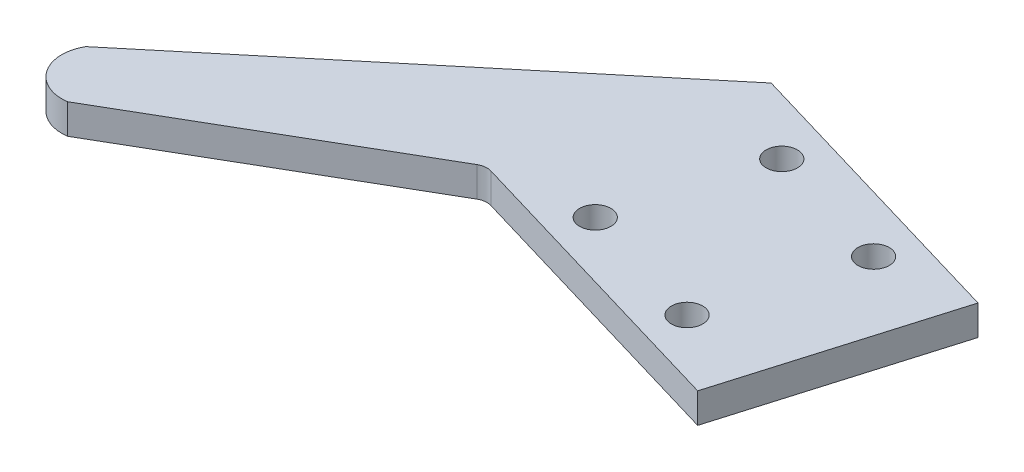
SolidWorks part; units mm, degrees
material "6061 Alloy"
ref_plane "Front Plane" through (0, 0, 0) normal (0, 0, 1) x (1, 0, 0)
ref_plane "Top Plane" through (0, 0, 0) normal (0, 1, 0) x (1, 0, 0)
ref_plane "Right Plane" through (0, 0, 0) normal (1, 0, 0) x (0, 0, -1)
sketch "Sketch1" plane through (0, 0, 0) normal (0, 1, 0) x (1, 0, 0)
  line L1 (22.9946, -31.525) -> (-18.2047, -55.4154)
  line L4 (81.9229, -10.7327) -> (71.7331, -45.1328)
  line L5 (71.7331, -45.1328) -> (24.9902, -31.2869)
  line L6 (81.9229, -10.7327) -> (35.1799, 3.1132)
  line L7 (35.1799, 3.1132) -> (-24.3516, -46.3783)
  arc A0 (-18.2047, -55.4154) -> (-24.3516, -46.3783) centre (-19.075, -49.3983) cw
  arc A2 (22.9946, -31.525) -> (24.9902, -31.2869) centre (24.2688, -33.7223) cw
  dimension "D1" = 2.54
  dimension "D2" = 35.8775
  dimension "D3" = 47.625
extrude "Boss-Extrude1" add sketch "Sketch1" along normal blind 4.7625
sketch "Sketch2" plane through (0, 4.7625, 0) normal (0, 1, 0) x (1, 0, 0)
  line L0 (35.1799, 3.1132) -> (71.7331, -45.1328) construction
  line L1 (53.4565, -21.0098) -> (63.8314, -24.083) construction
  line L3 (63.8314, -24.083) -> (67.2219, -12.6366) construction
  line L6 (63.8314, -24.083) -> (60.4408, -35.5294) construction
  line L7 (53.4565, -21.0098) -> (43.0817, -17.9366) construction
  line L8 (43.0817, -17.9366) -> (46.4723, -6.4903) construction
  line L9 (43.0817, -17.9366) -> (39.6911, -29.383) construction
  line L10 (53.4565, -21.0098) -> (58.5514, -3.8098) construction
  line L11 (81.9229, -10.7327) -> (35.1799, 3.1132) construction
  dimension "D1" = 21.6408
hole_wizard "#10 Clearance Hole1" positions "Sketch3" profile "Sketch4" hole size "#10" standard "ANSI Inch" end condition through all
sketch "Sketch3" plane through (0, 4.7625, 0) normal (0, 1, 0) x (1, 0, 0)
  point P0 (39.6911, -29.383)
  point P3 (46.4723, -6.4903)
  point P6 (67.2219, -12.6366)
  point P9 (60.4408, -35.5294)
sketch "Sketch4" plane through (39.6911, 4.7625, 29.383) normal (1, 0, 0) x (0, 0, 1)
  line L0 (0, 0) -> (0, 4.7625)
  line L1 (0, 4.7625) -> (2.4892, 4.7625)
  line L2 (2.4892, 4.7625) -> (2.4892, 0)
  line L5 (2.4892, 0) -> (0, 0)
  line L11 (0, -6.35) -> (0, 107.95) construction
  dimension "Thru Hole Dia." = 4.9784
  dimension "Thru Hole Depth" = 4.7625
